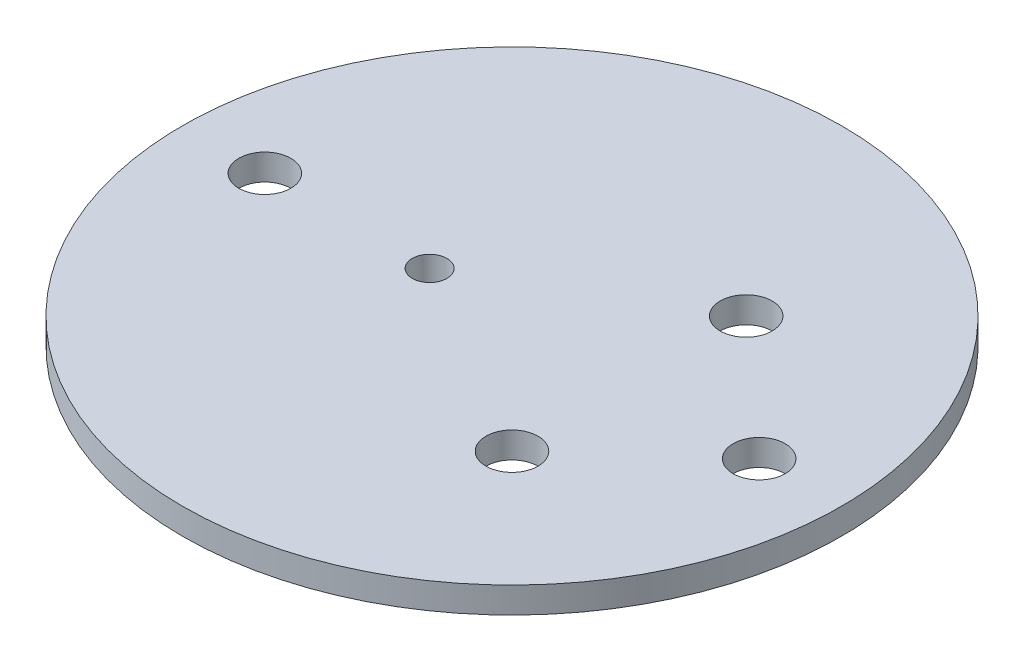
SolidWorks part; units mm, degrees
ref_plane "Front Plane" through (0, 0, 0) normal (0, 0, 1) x (1, 0, 0)
ref_plane "Top Plane" through (0, 0, 0) normal (0, 1, 0) x (1, 0, 0)
ref_plane "Right Plane" through (0, 0, 0) normal (1, 0, 0) x (0, 0, -1)
sketch "Sketch1" plane through (0, 0, 0) normal (0, 1, 0) x (1, 0, 0)
  line L0 (-28.5, 0) -> (28.5, 0) construction
  line L1 (13.5, 0) -> (13.5, 13.5)
  line L2 (13.5, 0) -> (13.5, -13.5)
  circle A1 centre (28.5, 0) radius 3
  circle A2 centre (-28.5, 0) radius 3
  circle A3 centre (13.5, 13.5) radius 3
  circle A4 centre (13.5, -13.5) radius 3
  circle A5 centre (-28.5, 0) radius 6.25 construction
  circle A6 centre (13.5, 13.5) radius 12.5 construction
  circle A7 centre (13.5, -13.5) radius 12.5 construction
  circle A8 centre (28.5, 0) radius 6.25 construction
  circle A9 centre (0, 0) radius 38
  circle A10 centre (-9.5, 0) radius 2
  circle A11 centre (-9.5, 0) radius 12.5 construction
  point P2 (-10.3816, 0)
  point P11 (0, 0)
  point P22 (-9.3718, 0)
  dimension "D1" = 76
  dimension "D3" = 6
  dimension "D4" = 13.5
  dimension "D5" = 6
  dimension "D6" = 12.5
  dimension "D7" = 25
  dimension "D8" = 4
  dimension "D9" = 25
  dimension "D2" = 57
  dimension "D10" = 9.5
  dimension "D11" = 13.5
extrude "Boss-Extrude1" add sketch "Sketch1" against normal blind 3 contours A4 A3 A2 A1 region at (-0.146, 0, 0)
